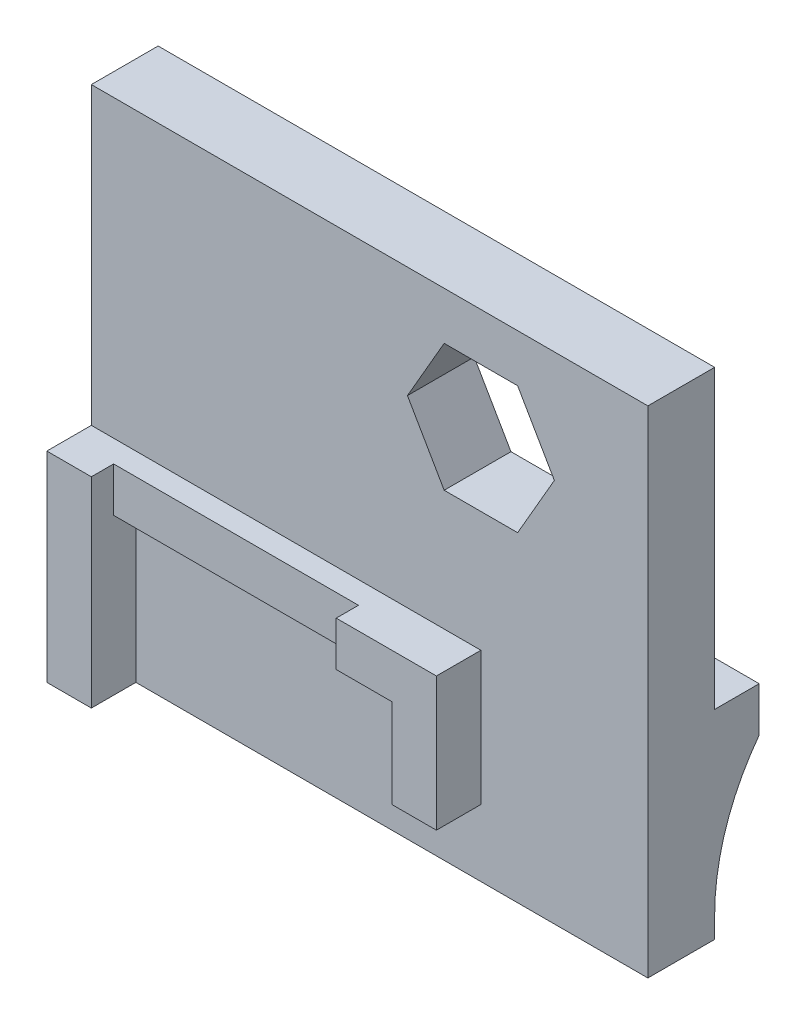
SolidWorks part; units mm, degrees
ref_plane "Plan de face" through (0, 0, 0) normal (0, 0, 1) x (1, 0, 0)
ref_plane "Plan de dessus" through (0, 0, 0) normal (0, 1, 0) x (1, 0, 0)
ref_plane "Plan de droite" through (0, 0, 0) normal (1, 0, 0) x (0, 0, -1)
sketch "Esquisse1" plane through (0, 0, 0) normal (0, 0, 1) x (1, 0, 0)
  line L1 (1.65, -2.8579) -> (3.3, 0)
  line L2 (3.3, 0) -> (1.65, 2.8579)
  line L3 (1.65, 2.8579) -> (-1.65, 2.8579)
  line L4 (-1.65, 2.8579) -> (-3.3, 0)
  line L5 (-3.3, 0) -> (-1.65, -2.8579)
  line L6 (-1.65, -2.8579) -> (1.65, -2.8579)
  line L7 (-17.5, 5) -> (7.5, 5)
  line L8 (-17.5, 5) -> (-17.5, -17.2579)
  line L9 (-17.5, -17.2579) -> (7.5, -17.2579)
  line L10 (7.5, 5) -> (7.5, -17.2579)
  circle A0 centre (0, 0) radius 2.8579 construction
  dimension "D1" = 3.3
  dimension "D2" = 25
  dimension "D3" = 14.4
  dimension "D4" = 5
  dimension "D5" = 17.5
extrude "Boss.-Extru.1" add sketch "Esquisse1" along normal blind 3
sketch "Esquisse2" plane through (0, 0, 0) normal (0, 0, -1) x (-1, 0, 0)
  line L0 (17.5, 5) -> (17.5, -17.2579) construction
  line L1 (17.5, -8.3079) -> (-7.5, -8.3079)
  line L2 (17.5, -8.3079) -> (17.5, -10.3079)
  line L3 (17.5, -10.3079) -> (-7.5, -10.3079)
  line L4 (-7.5, -8.3079) -> (-7.5, -10.3079)
  line L5 (-7.5, -17.2579) -> (-7.5, 5) construction
  line L6 (1.65, -2.8579) -> (-1.65, -2.8579) construction
  dimension "D1" = 5.45
  dimension "D2" = 2
extrude "Boss.-Extru.2" add sketch "Esquisse2" along normal blind 2
sketch "Esquisse3" plane through (0, 0, 3) normal (0, 0, 1) x (1, 0, 0)
  line L1 (-17.5, -8.2579) -> (0, -8.2579)
  line L2 (-17.5, -8.2579) -> (-17.5, -17.2579)
  line L4 (0, -8.2579) -> (0, -14.2579)
  line L5 (-15.5, -10.2579) -> (-2, -10.2579)
  line L6 (-15.5, -10.2579) -> (-15.5, -17.2579)
  line L8 (-2, -10.2579) -> (-2, -14.2579)
  line L9 (-17.5, -17.2579) -> (-15.5, -17.2579)
  line L10 (-17.5, -17.2579) -> (7.5, -17.2579) construction
  line L11 (-2, -14.2579) -> (0, -14.2579)
  line L13 (-17.5, 5) -> (-17.5, -17.2579) construction
  dimension "D1" = 13.5
  dimension "D2" = 4
  dimension "D3" = 7
  dimension "D4" = 2
  dimension "D5" = 2
  dimension "D6" = 2
extrude "Boss.-Extru.3" add sketch "Esquisse3" along normal blind 2
sketch "Esquisse4" [suppressed] plane through (0, 0, 5) normal (0, 0, 1) x (1, 0, 0)
  line L0 (-5.5, -17.2579) -> (17.5, -17.2579) construction
  line L1 (-3.5, -16.2579) -> (15.5, -16.2579)
  line L2 (-3.5, -16.2579) -> (-3.5, -17.2579)
  line L3 (-3.5, -17.2579) -> (15.5, -17.2579)
  line L4 (15.5, -16.2579) -> (15.5, -17.2579)
  line L5 (15.5, -17.2579) -> (15.5, -9.2579) construction
extrude "Enlèv. mat.-Extru.1" [suppressed] cut sketch "Esquisse4" against normal blind 2
sketch "Esquisse5" plane through (0, 0, 3) normal (0, 0, 1) x (1, 0, 0)
  line L1 (-15.5, -10.2579) -> (-1.3673, -10.2579)
  line L2 (-15.5, -10.2579) -> (-15.5, -15.6051)
  line L3 (-15.5, -15.6051) -> (-1.3673, -15.6051)
  line L4 (-1.3673, -10.2579) -> (-1.3673, -15.6051)
extrude "Boss.-Extru.4" [suppressed] add sketch "Esquisse5" along normal blind 2
sketch "Esquisse6" plane through (0, 0, 5) normal (0, 0, 1) x (1, 0, 0)
  line L0 (-2, -10.2579) -> (-2, -14.2579) construction
  line L5 (0, -8.2579) -> (-17.5, -8.2579) construction
  line L6 (-15.5, -8.2579) -> (-4.5, -8.2579)
  line L7 (-15.5, -8.2579) -> (-15.5, -10.2579)
  line L8 (-15.5, -10.2579) -> (-4.5, -10.2579)
  line L9 (-4.5, -8.2579) -> (-4.5, -10.2579)
  line L10 (-2, -10.2579) -> (-15.5, -10.2579) construction
  dimension "D1" = 11
  dimension "D2" = 2.5
extrude "Enlèv. mat.-Extru.2" cut sketch "Esquisse6" against normal blind 1
fillet "Congé1" radius 10 1 edges at (-5, -10.3079, 0)
